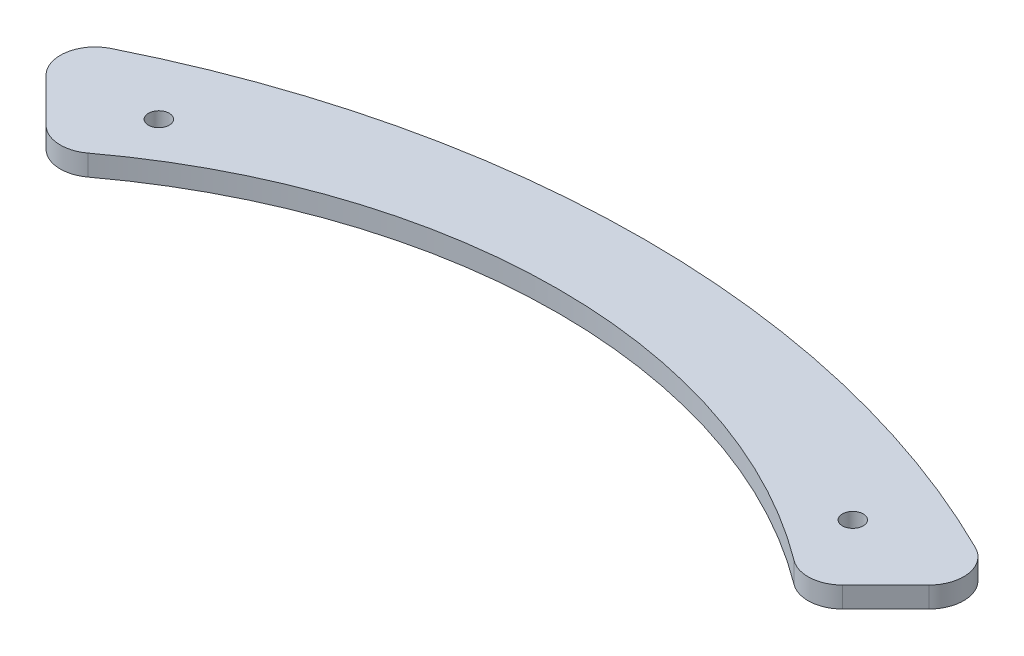
SolidWorks part; units mm, degrees
material "1060 Alloy"
ref_plane "Front Plane" through (0, 0, 0) normal (0, 0, 1) x (1, 0, 0)
ref_plane "Top Plane" through (0, 0, 0) normal (0, 1, 0) x (1, 0, 0)
ref_plane "Right Plane" through (0, 0, 0) normal (1, 0, 0) x (0, 0, -1)
sketch "Sketch1" plane through (0, 0, 0) normal (0, 1, 0) x (1, 0, 0)
  line L0 (-68.4085, 122.1486) -> (-54.2663, 108.0065)
  line L1 (68.4085, 122.1486) -> (54.2663, 108.0065)
  line L3 (0, 0) -> (-117.9329, 117.9329) construction
  line L4 (0, 0) -> (118.2874, 118.2874) construction
  line L5 (0, 0) -> (0, 174.1104) construction
  line L6 (-15, 127.1181) -> (15, 127.1181) construction
  line L7 (-15, 127.1181) -> (-15, 116.1181) construction
  line L8 (-15, 116.1181) -> (15, 116.1181) construction
  line L9 (15, 127.1181) -> (15, 116.1181) construction
  arc A0 (-68.4085, 122.1486) -> (68.4085, 122.1486) centre (0, 0) cw
  arc A1 (-54.2663, 108.0065) -> (54.2663, 108.0065) centre (0, 42.5835) cw
  circle A2 centre (0, 0) radius 128 construction
  dimension "D1" = 140
  dimension "D6" = 85
  dimension "D7" = 12
  dimension "D2" = 20
  dimension "D3" = 45
  dimension "D4" = 38
  dimension "D5" = 38
  dimension "D8" = 11
  dimension "D9" = 30
extrude "Boss-Extrude1" add sketch "Sketch1" along normal blind 3
fillet "Fillet1" radius 5 4 edges at (68.4085, 1.5, -122.1486) (54.2663, 1.5, -108.0065) (-68.4085, 1.5, -122.1486) (-54.2663, 1.5, -108.0065)
sketch "Sketch2" plane through (0, 3, 0) normal (0, 1, 0) x (1, 0, 0)
  circle A0 centre (-50, 120) radius 1.5
  circle A1 centre (50, 120) radius 1.5
  dimension "D1" = 3
  dimension "D2" = 120
  dimension "D3" = 50
  dimension "D4" = 50
extrude "Cut-Extrude1" cut sketch "Sketch2" against normal up to next
